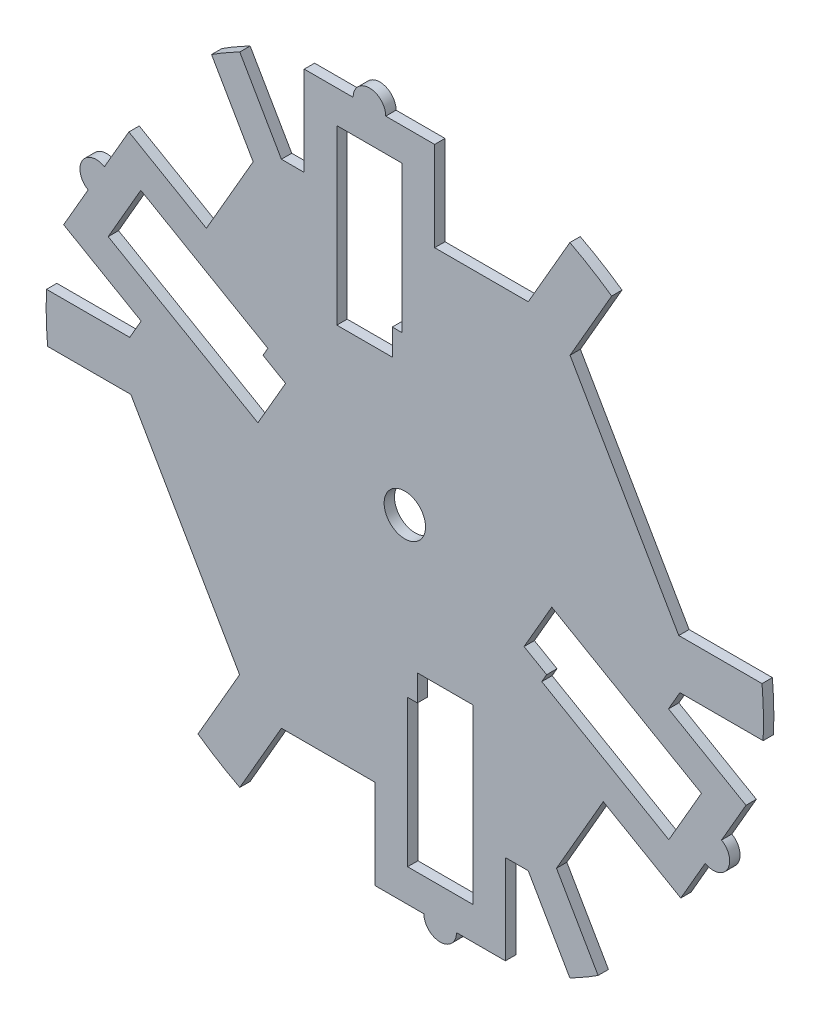
SolidWorks part; units mm, degrees
note: '?' marks a value the reader was unsure of.
ref_plane "Front Plane" through (0, 0, 0) normal (0, 0, 1) x (1, 0, 0)
ref_plane "Top Plane" through (0, 0, 0) normal (0, 1, 0) x (1, 0, 0)
ref_plane "Right Plane" through (0, 0, 0) normal (1, 0, 0) x (0, 0, -1)
sketch "Sketch1" plane through (0, 0, 0) normal (0, 0, 1) x (1, 0, 0)
  line L0 (-6.35, 0) -> (-6.35, 42.8001) construction
  line L1 (-6.35, 40) -> (-3.85, 40)
  line L2 (-3.85, 40) -> (-3.85, 48)
  line L3 (-3.85, 48) -> (-0.85, 48)
  line L4 (-0.85, 48) -> (-0.85, 93)
  line L5 (-0.85, 93) -> (-20.85, 93)
  line L6 (-20.85, 93) -> (-20.85, 40)
  line L7 (-20.85, 40) -> (-18.35, 40)
  line L8 (-18.35, 40) -> (-6.35, 40)
  line L9 (-6.35, 40) -> (-6.35, 0)
  line L10 (6.35, -40) -> (3.85, -40)
  line L11 (3.85, -40) -> (3.85, -48)
  line L12 (3.85, -48) -> (0.85, -48)
  line L13 (0.85, -48) -> (0.85, -93)
  line L14 (0.85, -93) -> (20.85, -93)
  line L15 (20.85, -93) -> (20.85, -40)
  line L16 (20.85, -40) -> (18.35, -40)
  line L17 (18.35, -40) -> (6.35, -40)
  line L18 (-3.85, 40) -> (3.85, -40) construction
  line L19 (37.816, -14.5007) -> (36.566, -16.6658)
  line L20 (36.566, -16.6658) -> (43.4942, -20.6658)
  line L21 (43.4942, -20.6658) -> (41.9942, -23.2639)
  line L22 (41.9942, -23.2639) -> (80.9654, -45.7639)
  line L23 (80.9654, -45.7639) -> (90.9654, -28.4434)
  line L24 (90.9654, -28.4434) -> (45.066, -1.9434)
  line L25 (45.066, -1.9434) -> (43.816, -4.1084)
  line L26 (43.816, -4.1084) -> (37.816, -14.5007)
  line L27 (0, 0) -> (3.85, -40) construction
  line L28 (0, 0) -> (36.566, -16.6658) construction
  line L29 (-37.816, 14.5007) -> (-36.566, 16.6658)
  line L30 (-36.566, 16.6658) -> (-43.4942, 20.6658)
  line L31 (-43.4942, 20.6658) -> (-41.9942, 23.2639)
  line L32 (-41.9942, 23.2639) -> (-80.9654, 45.7639)
  line L33 (-80.9654, 45.7639) -> (-90.9654, 28.4434)
  line L34 (-90.9654, 28.4434) -> (-45.066, 1.9434)
  line L35 (-45.066, 1.9434) -> (-43.816, 4.1084)
  line L36 (-43.816, 4.1084) -> (-37.816, 14.5007)
  line L37 (-36.566, 16.6658) -> (0, 0) construction
  circle A0 centre (0, 0) radius 110
  circle A1 centre (0, 0) radius 6.35
  point P14 (-6.35, 0)
  point P27 (0, 0)
  point P46 (0, 0)
  dimension "D5" = 12.7
  dimension "D11" = 220
  dimension "D1" = 17
  dimension "D2" = 12
  dimension "D3" = 53
  dimension "D4" = 45
  dimension "D6" = 20
  dimension "D7" = 40
  dimension "D10" = 60
  dimension "D8" = 2
  dimension "D9" = 2
  dimension "D12" = 2
extrude "Boss-Extrude1" add sketch "Sketch1" along normal mid plane 3.175
sketch "Sketch2" plane through (0, 0, 1.5875) normal (0, 0, 1) x (1, 0, 0)
  line L0 (0.85, -93) -> (20.85, -93) construction
  line L1 (10.85, -93) -> (10.85, -115.7637) construction
  line L2 (0, 0) -> (45.6639, 0) construction
  line L3 (-50.613, -97.6643) -> (-37.85, -75.5581)
  line L4 (-37.85, -75.5581) -> (-9.15, -75.5581)
  line L5 (-9.15, -75.5581) -> (-9.15, -103)
  line L6 (-9.15, -103) -> (5.85, -103)
  line L7 (30.85, -103) -> (30.85, -75.5581)
  line L8 (30.85, -75.5581) -> (37.85, -75.5581)
  line L9 (37.85, -75.5581) -> (50.613, -97.6643)
  line L10 (0.85, -48) -> (0.85, -93) construction
  line L11 (20.85, -93) -> (20.85, -40) construction
  line L12 (0, 0) -> (0, -249.0671) construction
  line L13 (0, -1.7463) -> (0, 1.7463) construction
  line L14 (0, 0) -> (55, -95.2628) construction
  line L15 (0, 0) -> (-55, -95.2628) construction
  line L16 (15.85, -103) -> (30.85, -103)
  arc A0 (-50.613, -97.6643) -> (50.613, -97.6643) centre (0, 0) ccw
  circle A1 centre (0, 0) radius 110 construction
  circle A2 centre (0, 0) radius 110 construction
  arc A3 (5.85, -103) -> (15.85, -103) centre (10.85, -103) ccw
  dimension "D1" = 10
  dimension "D2" = 10
  dimension "D3" = 60
  dimension "D4" = 10
  dimension "D5" = 7
  dimension "D6" = 10
  dimension "D7" = 5
extrude "Cut-Extrude3" cut sketch "Sketch2" against normal through all
ref_axis "Axis1" through (0, 0, 1.7463) along (0, 0, -1)?
pattern_circular "CirPattern1" count 2 over 360 about axis through (0, 0, 0) along (0, 0, 1) of "Cut-Extrude3"
pattern_circular "CirPattern2" count 2 every 60 about axis through (0, 0, 0) along (0, 0, 1) of "CirPattern1", "Cut-Extrude3"
sketch "Sketch5" plane through (0, 0, 1.5875) normal (0, 0, 1) x (1, 0, 0)
  line L0 (0, 0) -> (-116.0514, -67.0023) construction
  line L1 (0, 0) -> (-136.1412, 0) construction
  line L2 (-109.5445, -10) -> (-84.0145, -10)
  line L3 (-84.0145, -10) -> (-50.6675, -67.7587)
  line L4 (-50.6675, -67.7587) -> (-63.4325, -89.8683)
  line L5 (1.7463, 0) -> (-1.7463, 0) construction
  line L6 (0, 0) -> (-76.6401, -132.7445) construction
  line L7 (109.5445, 10) -> (84.0145, 10)
  line L8 (84.0145, 10) -> (50.6675, 67.7587)
  line L9 (50.6675, 67.7587) -> (63.4325, 89.8683)
  arc A0 (-63.4325, -89.8683) -> (-109.5445, -10) centre (0, 0) cw
  arc A1 (-109.8863, 5) -> (-50.613, -97.6643) centre (0, 0) ccw construction
  arc A2 (63.4325, 89.8683) -> (109.5445, 10) centre (0, 0) cw
  point P23 (0, 0)
  dimension "D1" = 10
  dimension "D3" = 25.53
  dimension "D2" = 2
extrude "Cut-Extrude5" cut sketch "Sketch5" against normal through all
